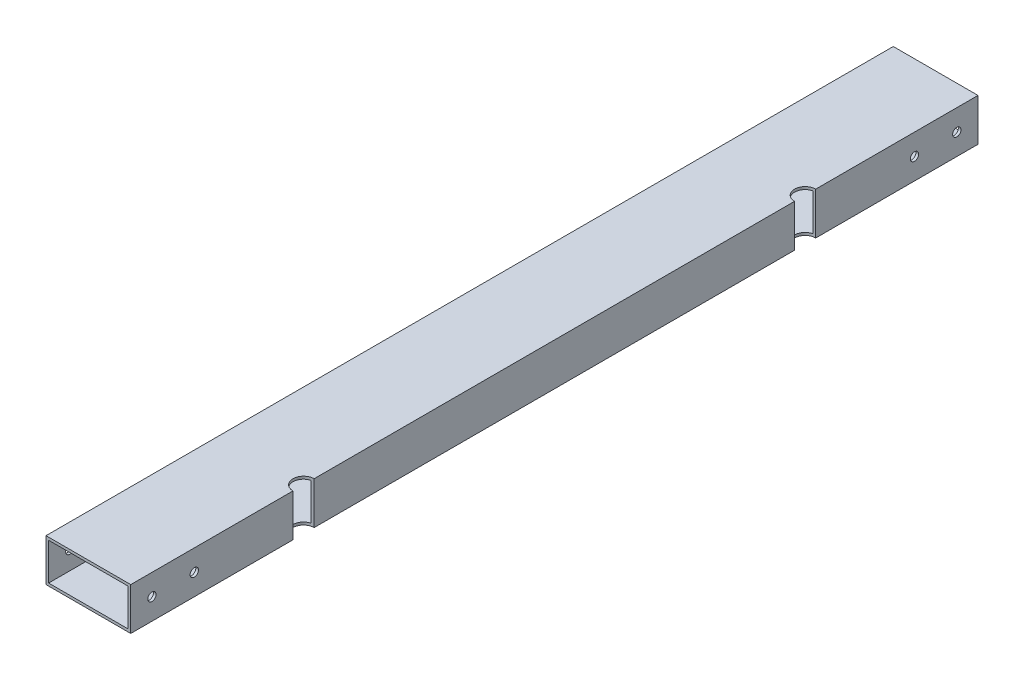
SolidWorks part; units mm, degrees
material "6061 Alloy"
ref_plane "Front Plane" through (0, 0, 0) normal (0, 0, 1) x (1, 0, 0)
ref_plane "Top Plane" through (0, 0, 0) normal (0, 1, 0) x (1, 0, 0)
ref_plane "Right Plane" through (0, 0, 0) normal (1, 0, 0) x (0, 0, -1)
sketch "Sketch1" plane through (0, 0, 0) normal (0, 0, 1) x (1, 0, 0)
  line L0 (-23.8125, 11.1125) -> (23.8125, 11.1125)
  line L2 (-25.4, 12.7) -> (25.4, 12.7)
  line L3 (-25.4, 12.7) -> (-25.4, -12.7)
  line L4 (-25.4, -12.7) -> (25.4, -12.7)
  line L5 (25.4, 12.7) -> (25.4, -12.7)
  line L10 (23.8125, 11.1125) -> (23.8125, -11.1125)
  line L11 (-23.8125, -11.1125) -> (23.8125, -11.1125)
  line L12 (-23.8125, 11.1125) -> (-23.8125, -11.1125)
  point P12 (0, 12.7)
  point P14 (25.4, 0)
  dimension "Wall Thickness" = 1.5875
  dimension "Outside Width" = 50.8
  dimension "Outside Height" = 25.4
  dimension "Inside Height" = 22.225
  dimension "Inside Width" = 47.625
sketch "Sketch2" plane through (0, 0, 0) normal (1, 0, 0) x (0, 0, -1)
  line L0 (254, 0) -> (-254, 0)
  point P4 (0, 0)
  point P7 (-254, 0)
  point P10 (254, 0)
  dimension "Length" = 508
sketch "Sketch3" plane through (0, 0, 0) normal (0, 0, 1) x (1, 0, 0)
  line L21 (25.4, 12.7) -> (-25.4, 12.7)
  line L22 (25.4, -12.7) -> (25.4, 12.7)
  line L23 (-25.4, -12.7) -> (25.4, -12.7)
  line L24 (-25.4, 12.7) -> (-25.4, -12.7)
  line L25 (25.4, 12.7) -> (-25.4, 12.7)
  line L26 (25.4, -12.7) -> (25.4, 12.7)
  line L27 (-25.4, -12.7) -> (25.4, -12.7)
  line L28 (-25.4, 12.7) -> (-25.4, -12.7)
  line L29 (23.8125, 11.1125) -> (-23.8125, 11.1125)
  line L30 (23.8125, -11.1125) -> (23.8125, 11.1125)
  line L31 (-23.8125, -11.1125) -> (23.8125, -11.1125)
  line L32 (-23.8125, 11.1125) -> (-23.8125, -11.1125)
  line L33 (23.8125, 11.1125) -> (-23.8125, 11.1125)
  line L34 (23.8125, -11.1125) -> (23.8125, 11.1125)
  line L35 (-23.8125, -11.1125) -> (23.8125, -11.1125)
  line L36 (-23.8125, 11.1125) -> (-23.8125, -11.1125)
  dimension "D1" = 0
  dimension "D2" = 0
extrude "Boss-Extrude1" add sketch "Sketch3" along normal up to vertex (254 mm away) and the other way up to vertex (254 mm away) up to point (0, 0, 254) other way up to point (0, 0, -254)
sketch "Drawing Reference" plane through (0, 0, 0) normal (1, 0, 0) x (0, 0, -1)
  line L0 (-254, 0) -> (254, 0) construction
  line L1 (0, -12.7) -> (0, 12.7) construction
  line L2 (-254, -12.7) -> (254, -12.7) construction
  line L5 (-254, 12.7) -> (254, 12.7) construction
  point P7 (-217.424, 0)
  point P8 (217.424, 0)
  dimension "D1" = 36.576
hole_wizard "#10 Clearance Hole1" positions "Sketch4" profile "Sketch5" hole size "#10" standard "ANSI Inch" end condition through all
sketch "Sketch4" plane through (25.4, 0, 0) normal (1, 0, 0) x (0, 0, -1)
  point P3 (-215.9, 0)
  point P12 (-241.3, 0)
  point P18 (215.9, 0)
  point P23 (241.3, 0)
  point P26 (241.3, 0)
  point P28 (-215.9, 0)
sketch "Sketch5" plane through (25.4, 0, 215.9) normal (0, 1, 0) x (0, 0, -1)
  line L0 (0, 0) -> (0, 50.8)
  line L1 (0, 50.8) -> (2.4892, 50.8)
  line L2 (2.4892, 50.8) -> (2.4892, 0)
  line L5 (2.4892, 0) -> (0, 0)
  line L11 (0, -6.35) -> (0, 107.95) construction
  dimension "Thru Hole Dia." = 4.9784
  dimension "Thru Hole Depth" = 50.8
sketch "Sketch6" plane through (0, 12.7, 0) normal (0, 1, 0) x (1, 0, 0)
  line L0 (25.4, -254) -> (25.4, -150.368) construction
  line L1 (25.4, -254) -> (25.4, 254) construction
  line L2 (25.4, 0) -> (42.2258, 0) construction
  circle A0 centre (25.4, -150.368) radius 6.35
  circle A1 centre (25.4, 150.368) radius 6.35
  dimension "D1" = 103.632
extrude "Cut-Extrude1" cut sketch "Sketch6" against normal through all
equation "\"D1@Drawing Reference\"=\"Outside Width@Sketch1\" * 0.72"
